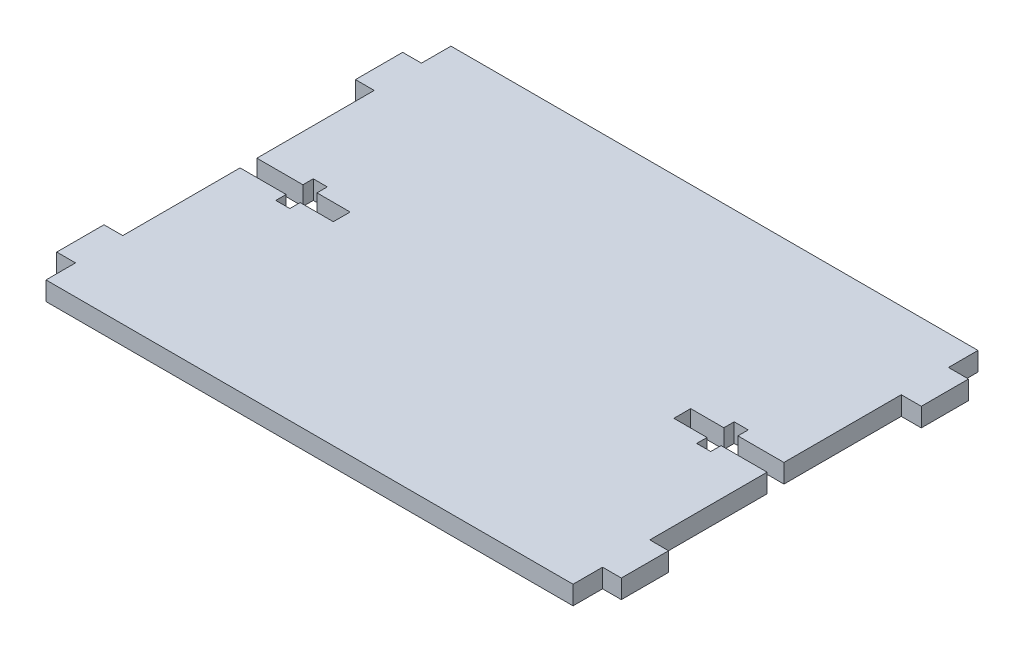
SolidWorks part; units mm, degrees
ref_plane "Front Plane" through (0, 0, 0) normal (0, 0, 1) x (1, 0, 0)
ref_plane "Top Plane" through (0, 0, 0) normal (0, 1, 0) x (1, 0, 0)
ref_plane "Right Plane" through (0, 0, 0) normal (1, 0, 0) x (0, 0, -1)
sketch "Sketch1" plane through (0, 0, 0) normal (0, 1, 0) x (1, 0, 0)
  line L1 (44.6419, 17.4753) -> (-44.6419, 17.4753)
  line L3 (-44.6419, -51.1247) -> (44.6419, -51.1247)
  line L8 (0, 17.4753) -> (0, 0) construction
  line L9 (0, 0) -> (0, -51.1247) construction
  line L16 (44.6419, 17.4753) -> (44.6419, 12.4753)
  line L17 (-44.6419, 17.4753) -> (-44.6419, 12.4753)
  line L18 (44.6419, 12.4753) -> (48.0336, 12.4753)
  line L19 (-44.6419, 12.4753) -> (-47.8219, 12.4753)
  line L20 (48.0336, 12.4753) -> (48.0336, 4.4753)
  line L21 (48.0336, 4.4753) -> (44.6419, 4.4753)
  line L22 (44.6419, 4.4753) -> (44.6419, -38.1247)
  line L23 (44.6419, -38.1247) -> (47.8219, -38.1247)
  line L24 (47.8219, -38.1247) -> (47.8219, -46.1247)
  line L25 (47.8219, -46.1247) -> (44.6419, -46.1247)
  line L26 (44.6419, -46.1247) -> (44.6419, -51.1247)
  line L27 (48.0336, 12.4753) -> (48.0336, 4.4753)
  line L28 (47.8219, -38.1247) -> (47.8219, -46.1247)
  line L34 (-47.8219, 12.4753) -> (-47.8219, 4.4753)
  line L36 (-47.8219, 4.4753) -> (-44.6419, 4.4753)
  line L37 (-44.6419, 4.4753) -> (-44.6419, -38.1247)
  line L38 (-44.6419, -38.1247) -> (-47.8219, -38.1247)
  line L39 (-47.8219, -38.1247) -> (-47.8219, -46.1247)
  line L40 (-47.8219, -46.1247) -> (-44.6419, -46.1247)
  line L41 (-44.6419, -46.1247) -> (-44.6419, -51.1247)
  point P3 (0, 0)
  point P4 (0, 0)
  dimension "D1" = 68.6
  dimension "D2" = 89.2838
extrude "Boss-Extrude1" add sketch "Sketch1" along normal blind 3.18 contours L40 L41 L3 L26 L25 L24 L23 L22 L21 L20 L18 L16 L1 L17 L19 L34 L36 L37 L38 L39 region at (0.013, 0, 16.8179)
sketch "Sketch2" plane through (0, 3.18, 0) normal (0, 1, 0) x (1, 0, 0)
  line L17 (-44.6419, 4.4753) -> (-44.6419, -38.1247) construction
  line L18 (-44.6419, -15.3997) -> (-36.8419, -15.3997)
  line L19 (-36.8419, -15.3997) -> (-36.8419, -13.6497)
  line L20 (-36.8419, -13.6497) -> (-34.4619, -13.6497)
  line L21 (-34.4619, -13.6497) -> (-34.4619, -15.3997)
  line L22 (-34.4619, -15.3997) -> (-28.8419, -15.3997)
  line L23 (-28.8419, -15.3997) -> (-28.8419, -18.2497)
  line L24 (-28.8419, -18.2497) -> (-34.4619, -18.2497)
  line L25 (-34.4619, -18.2497) -> (-34.4619, -19.9997)
  line L26 (-34.4619, -19.9997) -> (-36.8419, -19.9997)
  line L27 (-36.8419, -19.9997) -> (-36.8419, -18.2497)
  line L28 (-36.8419, -18.2497) -> (-44.6419, -18.2497)
  line L29 (-44.6419, -18.2497) -> (-44.6419, -15.3997)
  line L30 (-44.6419, -38.1247) -> (-47.8219, -38.1247) construction
  dimension "D1" = 15.8
  dimension "D2" = 2.85
  dimension "D3" = 2.38
  dimension "D4" = 7.8
  dimension "D5" = 19.875
  dimension "D6" = 6.35
extrude "Cut-Extrude1" cut sketch "Sketch2" against normal through all
mirror "Mirror1" about plane through (0, 0, 0) normal (1, 0, 0) of "Cut-Extrude1"
